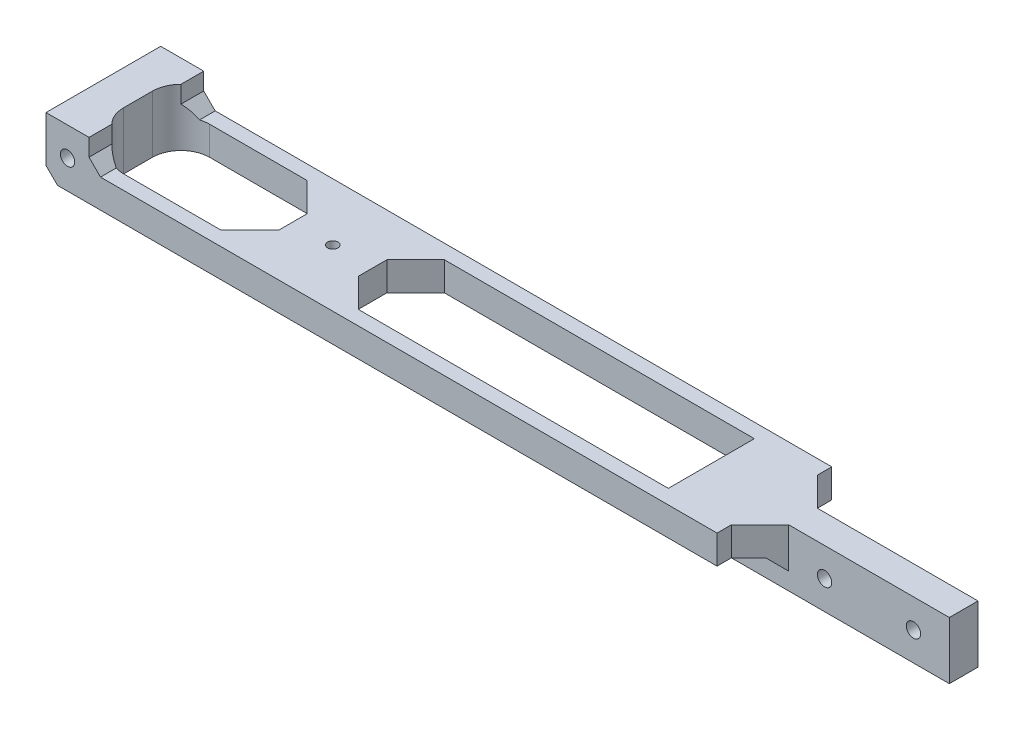
SolidWorks part; units mm, degrees
ref_plane "Front Plane" through (0, 0, 0) normal (0, 0, 1) x (1, 0, 0)
ref_plane "Top Plane" through (0, 0, 0) normal (0, 1, 0) x (1, 0, 0)
ref_plane "Right Plane" through (0, 0, 0) normal (1, 0, 0) x (0, 0, -1)
sketch "Sketch1" plane through (0, 0, 0) normal (0, 1, 0) x (1, 0, 0)
  line L0 (0, 0) -> (150, 0)
  line L1 (150, 20) -> (0, 20)
  line L2 (0, 20) -> (0, 0)
  line L3 (150, 20) -> (150, 0)
  line L4 (0, 10) -> (40, 10) construction
  circle A0 centre (40, 10) radius 0.9
  dimension "D4" = 1.8
  dimension "D1" = 150
  dimension "D2" = 20
  dimension "D3" = 40
extrude "Boss-Extrude1" add sketch "Sketch1" along normal blind 5
sketch "Sketch2" plane through (0, 0, 0) normal (0, -1, 0) x (1, 0, 0)
  circle A0 centre (40, -10) radius 1.95
  dimension "D1" = 3.9
extrude "Cut-Extrude1" cut sketch "Sketch2" against normal blind 2.9
sketch "Sketch3" plane through (0, 0, 0) normal (0, -1, 0) x (1, 0, 0)
  line L0 (150, -10) -> (129.1902, -10) construction
  line L1 (150, 0) -> (150, -20) construction
  line L2 (129.1902, -10) -> (107.4837, -10) construction
  line L3 (107.4837, -10) -> (94.4046, -10) construction
  line L4 (150, -20) -> (0, -20) construction
  line L5 (150, 0) -> (94.4046, 0)
  line L6 (150, 0) -> (150, -20)
  line L7 (150, -20) -> (94.4046, -20)
  line L8 (94.4046, 0) -> (94.4046, -20)
extrude "Boss-Extrude2" add sketch "Sketch3" along normal blind 5
sketch "Sketch5" plane through (0, 0, -20) normal (0, 0, -1) x (-1, 0, 0)
  line L0 (-150, 0) -> (-143.75, 0) construction
  line L1 (-150, 5) -> (-150, -5) construction
  line L2 (-143.75, 0) -> (-128.25, 0) construction
  line L3 (-128.25, 0) -> (-122, 0) construction
  circle A0 centre (-128.25, 0) radius 1.25
  circle A1 centre (-143.75, 0) radius 1.25
  dimension "D4" = 2.5
  dimension "D5" = 2.5
  dimension "D1" = 6.25
  dimension "D2" = 15.5
  dimension "D3" = 6.25
sketch "Sketch7" plane through (94.4046, 0, 0) normal (-1, 0, 0) x (0, 0, 1)
  line L1 (-20, -5) -> (0, -5)
  line L2 (-20, -5) -> (-20, 0)
  line L3 (-20, 0) -> (0, 0)
  line L4 (0, -5) -> (0, 0)
extrude "Cut-Extrude3" cut sketch "Sketch7" against normal blind 27.6
extrude "Cut-Extrude4" cut sketch "Sketch5" against normal blind 27.6
sketch "Sketch8" plane through (0, 5, 0) normal (0, 1, 0) x (1, 0, 0)
  line L0 (0, 10) -> (7.5, 10) construction
  line L1 (0, 20) -> (0, 0) construction
  line L2 (0, 0) -> (150, 0) construction
  line L3 (0, 20) -> (7.5, 20)
  line L4 (0, 20) -> (0, 0)
  line L5 (0, 0) -> (7.5, 0)
  line L6 (7.5, 20) -> (7.5, 0)
  dimension "D1" = 7.5
extrude "Boss-Extrude3" add sketch "Sketch8" along normal blind 5
sketch "Sketch9" plane through (0, 0, -20) normal (0, 0, -1) x (-1, 0, 0)
  line L0 (-3.75, 10) -> (-3.75, 0) construction
  line L1 (-7.5, 10) -> (0, 10) construction
  line L2 (-122.0046, 0) -> (0, 0) construction
  line L3 (0, 5) -> (-7.5, 5) construction
  line L4 (0, 10) -> (0, 0) construction
  circle A0 centre (-3.75, 5) radius 1.25
  dimension "D1" = 2.5
extrude "Cut-Extrude5" cut sketch "Sketch9" against normal blind 43
chamfer "Chamfer2" distance 2 distance2 2 1 edges
chamfer "Chamfer3" distance 2 angle 45 1 edges at (0, 0, -10)
chamfer "Chamfer4" distance 5 angle 45 1 edges at (122.0046, 0, -10)
sketch "Sketch12" plane through (0, 0, 0) normal (0, -1, 0) x (1, 0, 0)
  line L0 (117.0046, -10) -> (112.0046, -10) construction
  line L1 (117.0046, -20) -> (117.0046, 0) construction
  line L2 (41.95, -10) -> (46.95, -10) construction
  line L3 (38.05, -10) -> (33.05, -10) construction
  line L4 (57.3506, 0) -> (57.3506, -2.5) construction
  line L5 (2, 0) -> (117.0046, 0) construction
  line L6 (57.3506, -20) -> (57.3506, -17.5) construction
  line L7 (117.0046, -20) -> (2, -20) construction
  line L8 (0, -10) -> (5, -10) construction
  line L10 (112.0046, -2.5) -> (46.95, -2.5)
  line L11 (112.0046, -2.5) -> (112.0046, -17.5)
  line L12 (112.0046, -17.5) -> (46.95, -17.5)
  line L13 (46.95, -2.5) -> (46.95, -17.5)
  line L14 (33.05, -2.5) -> (6.0445, -2.5)
  line L15 (33.05, -2.5) -> (33.05, -17.5)
  line L16 (33.05, -17.5) -> (6.0445, -17.5)
  line L17 (6.0445, -2.5) -> (6.0445, -17.5)
  circle A0 centre (40, -10) radius 1.95 construction
  dimension "D1" = 5
  dimension "D2" = 5
  dimension "D3" = 5
  dimension "D4" = 5
  dimension "D5" = 2.5
  dimension "D6" = 2.5
extrude "Cut-Extrude33" cut sketch "Sketch12" against normal blind 43
fillet "Fillet3" radius 5 2 edges at (6.0445, 5, -17.5) (6.0445, 5, -2.5)
chamfer "Chamfer5" distance 5 angle 45 4 edges at (33.05, 2.5, -17.5) (33.05, 2.5, -2.5) (46.95, 2.5, -17.5) (46.95, 2.5, -2.5)
sketch "Sketch13" plane through (150, 0, 0) normal (1, 0, 0) x (0, 0, -1)
  line L0 (20, 0) -> (12.5, 0) construction
  line L1 (20, 5) -> (20, -5) construction
  line L2 (20, -5) -> (0, -5) construction
  line L3 (0, 5) -> (15, 5)
  line L4 (0, 5) -> (0, -5)
  line L5 (0, -5) -> (15, -5)
  line L7 (0, 0) -> (7.5, 0) construction
  line L8 (7.5, -5) -> (0, -5)
  line L9 (5, -5) -> (15, -5)
  line L10 (7.5, -5) -> (7.5, 5)
  line L11 (5, 5) -> (15, 5)
  line L12 (7.5, 5) -> (0, 5)
  line L13 (5, -5) -> (0, -5)
  line L14 (0, -5) -> (0, 5)
  line L15 (5, 5) -> (0, 5)
  line L16 (0, -5) -> (0, 5)
  line L17 (20, 5) -> (15, 5)
  line L18 (20, 5) -> (20, -5)
  line L19 (20, -5) -> (15, -5)
  line L20 (20, 5) -> (12.5, 5)
  line L21 (20, 5) -> (20, -5)
  line L22 (20, -5) -> (12.5, -5)
  line L23 (12.5, 5) -> (12.5, -5)
  line M7 (0, 5) -> (0, -5)
  line M8 (0, -5) -> (20, -5)
  line M9 (20, -5) -> (20, 5)
  line M10 (20, 5) -> (0, 5)
  dimension "D1" = 7.5
  dimension "D2" = 7.5
extrude "Cut-Extrude35" cut sketch "Sketch13" against normal blind 34 contours L8 L10 L3 M10 M7 M8 | L23 L9 M10 M8 M9 region at (150, 0, -3.75) region at (150, 0, -16.25)
sketch "Sketch14" plane through (112.0046, 0, 0) normal (-1, 0, 0) x (0, 0, 1)
  line L1 (-2.5, 0) -> (-17.5, 0)
  line L2 (-2.5, 0) -> (-2.5, 5)
  line L3 (-2.5, 5) -> (-17.5, 5)
  line L4 (-17.5, 0) -> (-17.5, 5)
extrude "Boss-Extrude4" add sketch "Sketch14" along normal blind 6
sketch "Sketch15" plane through (106.0046, 0, 0) normal (-1, 0, 0) x (0, 0, 1)
  line L0 (-10, 0) -> (-10, 5) construction
  line L1 (-17.5, 0) -> (-2.5, 0) construction
  line L2 (-2.5, 5) -> (-17.5, 5) construction
  line L3 (-10, 5) -> (-7.5, 5)
  line L4 (-7.5, 5) -> (-7.5, -5)
  line L5 (-7.5, -5) -> (-12.5, -5)
  line L6 (-12.5, -5) -> (-12.5, 5)
  line L7 (-12.5, 5) -> (-10, 5)
  dimension "D1" = 2.5
  dimension "D2" = 10
  dimension "D3" = 5
  dimension "D4" = 10
extrude "Boss-Extrude5" add sketch "Sketch15" against normal blind 18
chamfer "Chamfer7" distance 2 angle 45 3 edges at (111.0023, 0, -7.5) (106.0046, -5, -10) (111.0023, 0, -12.5)
sketch "Sketch16" plane through (0, 0, -7.5) normal (0, 0, 1) x (1, 0, 0)
  line L0 (150, 0) -> (117, 0) construction
  line L1 (150, -5) -> (150, 5) construction
  dimension "D1" = 33
sketch "Sketch17" plane through (116, 0, 0) normal (1, 0, 0) x (0, 0, -1)
  line L10 (0, 0) -> (5.5, 0)
  line L11 (5.5, 0) -> (7.5, -2)
  line L12 (7.5, -2) -> (7.5, 5)
  line L13 (7.5, 5) -> (0, 5)
  line L14 (0, 5) -> (0, 0)
  line L15 (0, 0) -> (5.5, 0)
  line L16 (5.5, 0) -> (7.5, -2)
  line L17 (7.5, -2) -> (7.5, 5)
  line L18 (7.5, 5) -> (0, 5)
  line L19 (0, 5) -> (0, 0)
  line L25 (12.5, 5) -> (12.5, -2)
  line L26 (12.5, -2) -> (14.5, 0)
  line L27 (14.5, 0) -> (20, 0)
  line L28 (20, 0) -> (20, 5)
  line L29 (20, 5) -> (12.5, 5)
  line L30 (12.5, 5) -> (12.5, -2)
  line L31 (12.5, -2) -> (14.5, 0)
  line L32 (14.5, 0) -> (20, 0)
  line L33 (20, 0) -> (20, 5)
  line L34 (20, 5) -> (12.5, 5)
  dimension "D1" = 0
  dimension "D2" = 0
extrude "Boss-Extrude6" add sketch "Sketch17" along normal up to vertex (1 mm away) up to point (117, 0, -7.5)
chamfer "Chamfer8" distance 5 angle 45 2 edges at (117, 1.5, -12.5) (117, 1.5, -7.5)
